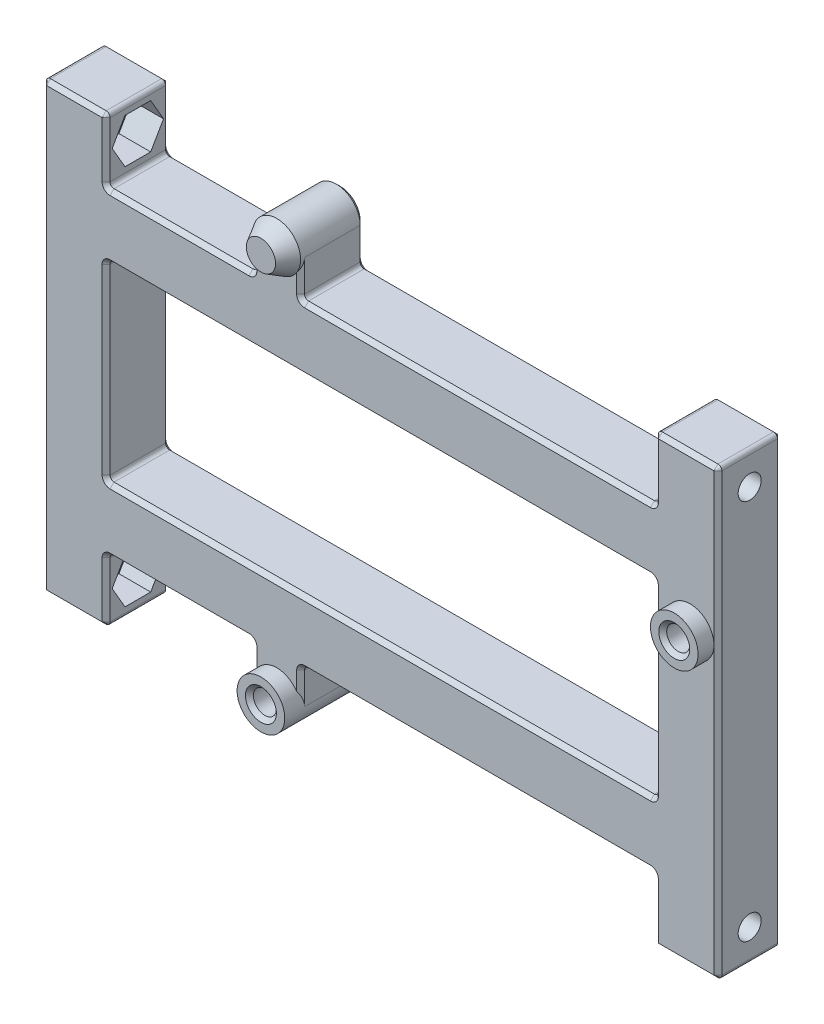
SolidWorks part; units mm, degrees
ref_plane "Płaszczyzna przednia" through (0, 0, 0) normal (0, 0, 1) x (1, 0, 0)
ref_plane "Płaszczyzna górna" through (0, 0, 0) normal (0, 1, 0) x (1, 0, 0)
ref_plane "Płaszczyzna prawa" through (0, 0, 0) normal (1, 0, 0) x (0, 0, -1)
sketch "Szkic1" plane through (0, 0, 0) normal (0, 0, 1) x (1, 0, 0)
  line L0 (14, 2.55) -> (14, -7.95) construction
  line L1 (14, -7.95) -> (14, 27.05) construction
  circle A0 centre (66.05, 35.55) radius 1.45
  circle A2 centre (14, 2.55) radius 1.45
  circle A3 centre (14, 2.55) radius 3
  circle A5 centre (66.05, 35.55) radius 3
  point P0 (14, 2.55)
  point P2 (66.05, 35.55)
  dimension "D7" = 2.9
  dimension "D8" = 6
  dimension "D1" = 14
  dimension "D2" = 2.55
  dimension "D3" = 10.5
  dimension "D4" = 35
  dimension "D5" = 35.55
  dimension "D6" = 66.05
extrude "Dodanie-wyciągnięcie1" add sketch "Szkic1" along normal blind 10
sketch "Szkic2" plane through (0, 0, 0) normal (0, 0, 1) x (1, 0, 0)
  line L0 (14, 27.05) -> (27.025, 27.05) construction
  line L1 (11, 2.55) -> (11, 7.05)
  line L2 (69.55, 55.05) -> (-15.5, 55.05)
  line L3 (69.55, 55.05) -> (69.55, -0.95)
  line L4 (69.55, -0.95) -> (-15.5, -0.95)
  line L5 (-15.5, 55.05) -> (-15.5, -0.95)
  line L6 (69.55, 55.05) -> (-15.5, -0.95) construction
  line L7 (69.55, -0.95) -> (-15.5, 55.05) construction
  line L8 (-15.5, 55.05) -> (-7.5, 55.05)
  line L9 (-15.5, 55.05) -> (-15.5, -0.95)
  line L10 (-15.5, -0.95) -> (-7.5, -0.95)
  line L11 (-7.5, 55.05) -> (-7.5, -0.95)
  line L12 (69.55, 55.05) -> (61.55, 55.05)
  line L13 (69.55, 55.05) -> (69.55, -0.95)
  line L14 (69.55, -0.95) -> (61.55, -0.95)
  line L15 (61.55, 55.05) -> (61.55, -0.95)
  line L16 (-7.5, 7.05) -> (61.55, 7.05)
  line L17 (-7.5, 7.05) -> (-7.5, 15.05)
  line L18 (-7.5, 15.05) -> (61.55, 15.05)
  line L19 (61.55, 7.05) -> (61.55, 15.05)
  line L20 (-7.5, 47.05) -> (61.55, 47.05)
  line L21 (-7.5, 47.05) -> (-7.5, 39.05)
  line L22 (-7.5, 39.05) -> (61.55, 39.05)
  line L23 (61.55, 47.05) -> (61.55, 39.05)
  line L24 (11, 7.05) -> (17, 7.05)
  line L25 (17, 7.05) -> (17, 2.55)
  line L26 (17, 47.05) -> (17, 51.55)
  line L27 (11, 51.55) -> (11, 47.05)
  arc A0 (11, 2.55) -> (17, 2.55) centre (14, 2.55) ccw
  circle A1 centre (14, 2.55) radius 3 construction
  circle A2 centre (14, 2.55) radius 1.45 construction
  circle A3 centre (66.05, 35.55) radius 3 construction
  circle A4 centre (14, 2.55) radius 1.45
  circle A5 centre (66.05, 35.55) radius 3
  circle A6 centre (14, 51.55) radius 1.45
  arc A7 (11, 51.55) -> (17, 51.55) centre (14, 51.55) cw
  dimension "D1" = 56
  dimension "D2" = 3.5
  dimension "D3" = 29.5
  dimension "D4" = 8
  dimension "D5" = 8
  dimension "D6" = 8
  dimension "D7" = 8
  dimension "D8" = 8
  dimension "D9" = 8
extrude "Dodanie-wyciągnięcie2" add sketch "Szkic2" along normal blind 8 contours L11 L2 L5 L4 | L11 L22 L15 L20 | L18 L11 L16 L15 | L1 A0 L25 L16 A4 | L2 L15 L4 L3 A5 | A7 L27 L20 L26 A6 | A6
sketch "Szkic3" plane through (0, 0, 8) normal (0, 0, 1) x (1, 0, 0)
  circle A0 centre (14, 51.55) radius 3
extrude "Dodanie-wyciągnięcie3" add sketch "Szkic3" along normal blind 2 draft 30
sketch "Szkic4" plane through (-15.5, 0, 0) normal (-1, 0, 0) x (0, 0, 1)
  line L0 (4, 3.05) -> (4, -0.95) construction
  line L1 (8, -0.95) -> (0, -0.95) construction
  circle A0 centre (4, 3.05) radius 1.45
  dimension "D2" = 2.9
  dimension "D1" = 4
extrude "Wytnij-wyciągnięcie1" cut sketch "Szkic4" against normal up to next
sketch "Szkic5" plane through (-7.5, 0, 0) normal (1, 0, 0) x (0, 0, -1)
  line L1 (-0.7668, 3.05) -> (-2.3834, 5.85)
  line L2 (-2.3834, 5.85) -> (-5.6166, 5.85)
  line L3 (-5.6166, 5.85) -> (-7.2332, 3.05)
  line L4 (-7.2332, 3.05) -> (-5.6166, 0.25)
  line L5 (-5.6166, 0.25) -> (-2.3834, 0.25)
  line L6 (-2.3834, 0.25) -> (-0.7668, 3.05)
  circle A0 centre (-4, 3.05) radius 2.8 construction
  dimension "D1" = 5.6
extrude "Wytnij-wyciągnięcie2" cut sketch "Szkic5" against normal blind 4
ref_plane "Płaszczyzna1" through (27.025, 0, 0) normal (-1, 0, 0) x (0, 0, 1)
ref_plane "Płaszczyzna2" through (0, 27.05, 0) normal (0, -1, 0) x (-1, 0, 0)
mirror "Lustro1" about plane through (27.025, 0, 0) normal (-1, 0, 0) of "Wytnij-wyciągnięcie2", "Wytnij-wyciągnięcie1" second plane through (0, 27.05, 0) second plane normal (0, -1, 0)
fillet "Zaokrąglenie1" radius 0.5 20 edges at (61.55, 39.05, 4) (61.55, 15.05, 4) (-7.5, 15.05, 4) (17, 7.05, 4) (61.55, 7.05, 4) (61.55, -0.95, 4) (69.55, -0.95, 4) (69.55, 55.05, 4) (61.55, 55.05, 4) (61.55, 47.05, 4) (17, 47.05, 4) (11, 47.05, 4) (-7.5, 47.05, 4) (-7.5, 55.05, 4) (-15.5, 55.05, 4) (-15.5, -0.95, 4) (-7.5, -0.95, 4) (-7.5, 7.05, 4) (11, 7.05, 4) (-7.5, 39.05, 4)
chamfer "Sfazowanie1" distance 0.5 angle 45 88 edges at (14, -0.45, 0) (1.75, 47.05, 0) (1.75, 47.05, 8) (17, 49.55, 0) (17, 49.55, 8) (39.275, 47.05, 0) (39.275, 47.05, 8) (65.55, 55.05, 0) (65.55, 55.05, 8) (1.75, 7.05, 0) (-7.5, 3.05, 0) (-11.5, -0.95, 0) (-15.5, 27.05, 0) (-11.5, 55.05, 0) (11, 49.55, 8) (-7.5, 51.05, 0) (61.55, 51.05, 0) (69.55, 27.05, 0) (65.55, -0.95, 0) (61.55, 3.05, 0) (39.275, 7.05, 0) (17, 4.55, 0) (61.55, 27.05, 0) (27.025, 39.05, 0) (-7.5, 27.05, 0) (27.025, 15.05, 0) (-15.3536, 54.9036, 0) (-15.3536, -0.8036, 0) (-7.6464, -0.8036, 0) (61.6964, -0.8036, 0) (69.4036, -0.8036, 0) (-7.6464, 54.9036, 0) (61.6964, 54.9036, 0) (69.4036, 54.9036, 0) (69.55, 27.05, 8) (61.55, 27.05, 8) (27.025, 15.05, 8) (-7.5, 27.05, 8) (27.025, 39.05, 8) (-7.5, 51.05, 8) (-11.5, 55.05, 8) (-15.5, 27.05, 8) (-11.5, -0.95, 8) (-7.5, 3.05, 8) (1.75, 7.05, 8) (17, 4.55, 8) (39.275, 7.05, 8) (61.55, 3.05, 8) (65.55, -0.95, 8) (61.55, 51.05, 8) (-15.3536, 54.9036, 8) (-15.3536, -0.8036, 8) (11, 4.55, 0) (-7.6464, -0.8036, 8) (61.6964, -0.8036, 8) (69.4036, -0.8036, 8) (-7.6464, 54.9036, 8) (61.6964, 54.9036, 8) (69.4036, 54.9036, 8) (14, 54.55, 0) (10.8536, 47.1964, 0) (10.8536, 47.1964, 8) (17.1464, 47.1964, 0) (17.1464, 47.1964, 8) (61.4036, 47.1964, 0) (61.4036, 47.1964, 8) (61.4036, 15.1964, 0) (61.4036, 15.1964, 8) (-7.3536, 15.1964, 0) (-7.3536, 15.1964, 8) (-7.3536, 47.1964, 0) (-7.3536, 47.1964, 8) (-7.3536, 38.9036, 0) (-7.3536, 38.9036, 8) (61.4036, 38.9036, 0) (61.4036, 38.9036, 8) (61.4036, 6.9036, 0) (61.4036, 6.9036, 8) (17.1464, 6.9036, 0) (17.1464, 6.9036, 8) (10.8536, 6.9036, 0) (10.8536, 6.9036, 8) (-7.3536, 6.9036, 0) (-7.3536, 6.9036, 8) (11, 49.55, 0) (11, 4.55, 8) (15.45, 2.55, 10) (67.5, 35.55, 10)
